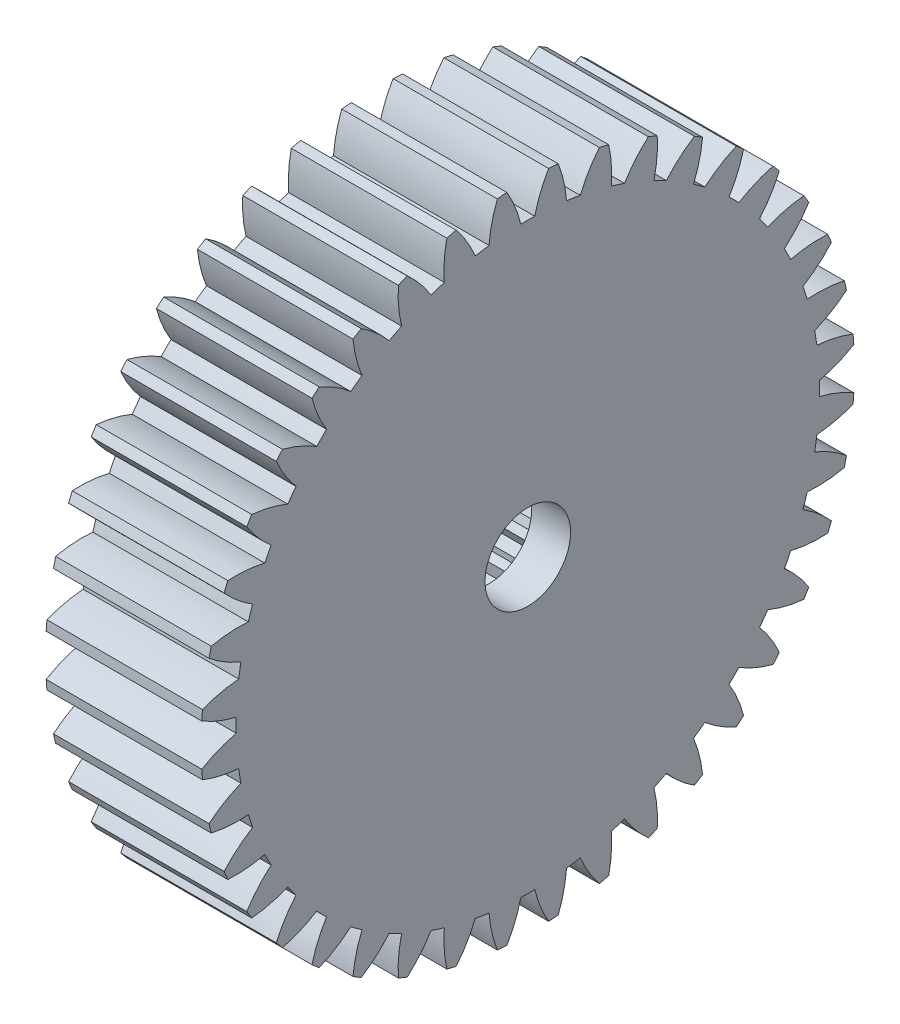
SolidWorks part; units mm, degrees
ref_plane "Front Plane" through (0, 0, 0) normal (0, 0, 1) x (1, 0, 0)
ref_plane "Top Plane" through (0, 0, 0) normal (0, 1, 0) x (1, 0, 0)
ref_plane "Right Plane" through (0, 0, 0) normal (1, 0, 0) x (0, 0, -1)
ref_plane "Plane1" through (-1.595, 0, 0) normal (1, 0, 0) x (0, 0, -1)
sketch "Sketch1" plane through (-1.595, 0, 0) normal (1, 0, 0) x (0, 0, -1)
  circle B0 centre (0, 0) radius 0.4
  arc B1 (-8.3829, 0.5357) -> (-7.4969, 0.179) centre (-6.7581, 3.2926) ccw
  arc B2 (-7.4969, 0.179) -> (-7.4969, -0.179) centre (0, 0) ccw
  arc B3 (-7.4969, -0.179) -> (-8.3829, -0.5357) centre (-6.7581, -3.2926) ccw
  arc B4 (-8.3829, -0.5357) -> (-8.3635, -0.7822) centre (0, 0) ccw
  arc B5 (-8.3635, -0.7822) -> (-7.4326, -0.996) centre (-7.19, 2.1948) ccw
  arc B6 (-7.4326, -0.996) -> (-7.3766, -1.3496) centre (0, 0) ccw
  arc B7 (-7.3766, -1.3496) -> (-8.1959, -1.8405) centre (-6.1599, -4.3092) ccw
  arc B8 (-8.1959, -1.8405) -> (-8.1382, -2.081) centre (0, 0) ccw
  arc B9 (-8.1382, -2.081) -> (-7.1853, -2.1464) centre (-7.4448, 1.043) ccw
  arc B10 (-7.1853, -2.1464) -> (-7.0746, -2.4869) centre (0, 0) ccw
  arc B11 (-7.0746, -2.4869) -> (-7.8071, -3.1) centre (-5.4099, -5.2198) ccw
  arc B12 (-7.8071, -3.1) -> (-7.7124, -3.3284) centre (0, 0) ccw
  arc B13 (-7.7124, -3.3284) -> (-6.761, -3.244) centre (-7.5163, -0.1344) ccw
  arc B14 (-6.761, -3.244) -> (-6.5985, -3.563) centre (0, 0) ccw
  arc B15 (-6.5985, -3.563) -> (-7.226, -4.2831) centre (-4.5268, -6.0018) ccw
  arc B16 (-7.226, -4.2831) -> (-7.0968, -4.4939) centre (0, 0) ccw
  arc B17 (-7.0968, -4.4939) -> (-6.1703, -4.2617) centre (-7.4028, -1.3086) ccw
  arc B18 (-6.1703, -4.2617) -> (-5.9599, -4.5514) centre (0, 0) ccw
  arc B19 (-5.9599, -4.5514) -> (-6.467, -5.3608) centre (-3.5321, -6.6361) ccw
  arc B20 (-6.467, -5.3608) -> (-6.3064, -5.5488) centre (0, 0) ccw
  arc B21 (-6.3064, -5.5488) -> (-5.4277, -5.1745) centre (-7.1069, -2.4505) ccw
  arc B22 (-5.4277, -5.1745) -> (-5.1745, -5.4277) centre (0, 0) ccw
  arc B23 (-5.1745, -5.4277) -> (-5.5488, -6.3064) centre (-2.4505, -7.1069) ccw
  arc B24 (-5.5488, -6.3064) -> (-5.3608, -6.467) centre (0, 0) ccw
  arc B25 (-5.3608, -6.467) -> (-4.5514, -5.9599) centre (-6.6361, -3.5321) ccw
  arc B26 (-4.5514, -5.9599) -> (-4.2617, -6.1703) centre (0, 0) ccw
  arc B27 (-4.2617, -6.1703) -> (-4.4939, -7.0968) centre (-1.3086, -7.4028) ccw
  arc B28 (-4.4939, -7.0968) -> (-4.2831, -7.226) centre (0, 0) ccw
  arc B29 (-4.2831, -7.226) -> (-3.563, -6.5985) centre (-6.0018, -4.5268) ccw
  arc B30 (-3.563, -6.5985) -> (-3.244, -6.761) centre (0, 0) ccw
  arc B31 (-3.244, -6.761) -> (-3.3284, -7.7124) centre (-0.1344, -7.5163) ccw
  arc B32 (-3.3284, -7.7124) -> (-3.1, -7.8071) centre (0, 0) ccw
  arc B33 (-3.1, -7.8071) -> (-2.4869, -7.0746) centre (-5.2198, -5.4099) ccw
  arc B34 (-2.4869, -7.0746) -> (-2.1464, -7.1853) centre (0, 0) ccw
  arc B35 (-2.1464, -7.1853) -> (-2.081, -8.1382) centre (1.043, -7.4448) ccw
  arc B36 (-2.081, -8.1382) -> (-1.8405, -8.1959) centre (0, 0) ccw
  arc B37 (-1.8405, -8.1959) -> (-1.3496, -7.3766) centre (-4.3092, -6.1599) ccw
  arc B38 (-1.3496, -7.3766) -> (-0.996, -7.4326) centre (0, 0) ccw
  arc B39 (-0.996, -7.4326) -> (-0.7822, -8.3635) centre (2.1948, -7.19) ccw
  arc B40 (-0.7822, -8.3635) -> (-0.5357, -8.3829) centre (0, 0) ccw
  arc B41 (-0.5357, -8.3829) -> (-0.179, -7.4969) centre (-3.2926, -6.7581) ccw
  arc B42 (-0.179, -7.4969) -> (0.179, -7.4969) centre (0, 0) ccw
  arc B43 (0.179, -7.4969) -> (0.5357, -8.3829) centre (3.2926, -6.7581) ccw
  arc B44 (0.5357, -8.3829) -> (0.7822, -8.3635) centre (0, 0) ccw
  arc B45 (0.7822, -8.3635) -> (0.996, -7.4326) centre (-2.1948, -7.19) ccw
  arc B46 (0.996, -7.4326) -> (1.3496, -7.3766) centre (0, 0) ccw
  arc B47 (1.3496, -7.3766) -> (1.8405, -8.1959) centre (4.3092, -6.1599) ccw
  arc B48 (1.8405, -8.1959) -> (2.081, -8.1382) centre (0, 0) ccw
  arc B49 (2.081, -8.1382) -> (2.1464, -7.1853) centre (-1.043, -7.4448) ccw
  arc B50 (2.1464, -7.1853) -> (2.4869, -7.0746) centre (0, 0) ccw
  arc B51 (2.4869, -7.0746) -> (3.1, -7.8071) centre (5.2198, -5.4099) ccw
  arc B52 (3.1, -7.8071) -> (3.3284, -7.7124) centre (0, 0) ccw
  arc B53 (3.3284, -7.7124) -> (3.244, -6.761) centre (0.1344, -7.5163) ccw
  arc B54 (3.244, -6.761) -> (3.563, -6.5985) centre (0, 0) ccw
  arc B55 (3.563, -6.5985) -> (4.2831, -7.226) centre (6.0018, -4.5268) ccw
  arc B56 (4.2831, -7.226) -> (4.4939, -7.0968) centre (0, 0) ccw
  arc B57 (4.4939, -7.0968) -> (4.2617, -6.1703) centre (1.3086, -7.4028) ccw
  arc B58 (4.2617, -6.1703) -> (4.5514, -5.9599) centre (0, 0) ccw
  arc B59 (4.5514, -5.9599) -> (5.3608, -6.467) centre (6.6361, -3.5321) ccw
  arc B60 (5.3608, -6.467) -> (5.5488, -6.3064) centre (0, 0) ccw
  arc B61 (5.5488, -6.3064) -> (5.1745, -5.4277) centre (2.4505, -7.1069) ccw
  arc B62 (5.1745, -5.4277) -> (5.4277, -5.1745) centre (0, 0) ccw
  arc B63 (5.4277, -5.1745) -> (6.3064, -5.5488) centre (7.1069, -2.4505) ccw
  arc B64 (6.3064, -5.5488) -> (6.467, -5.3608) centre (0, 0) ccw
  arc B65 (6.467, -5.3608) -> (5.9599, -4.5514) centre (3.5321, -6.6361) ccw
  arc B66 (5.9599, -4.5514) -> (6.1703, -4.2617) centre (0, 0) ccw
  arc B67 (6.1703, -4.2617) -> (7.0968, -4.4939) centre (7.4028, -1.3086) ccw
  arc B68 (7.0968, -4.4939) -> (7.226, -4.2831) centre (0, 0) ccw
  arc B69 (7.226, -4.2831) -> (6.5985, -3.563) centre (4.5268, -6.0018) ccw
  arc B70 (6.5985, -3.563) -> (6.761, -3.244) centre (0, 0) ccw
  arc B71 (6.761, -3.244) -> (7.7124, -3.3284) centre (7.5163, -0.1344) ccw
  arc B72 (7.7124, -3.3284) -> (7.8071, -3.1) centre (0, 0) ccw
  arc B73 (7.8071, -3.1) -> (7.0746, -2.4869) centre (5.4099, -5.2198) ccw
  arc B74 (7.0746, -2.4869) -> (7.1853, -2.1464) centre (0, 0) ccw
  arc B75 (7.1853, -2.1464) -> (8.1382, -2.081) centre (7.4448, 1.043) ccw
  arc B76 (8.1382, -2.081) -> (8.1959, -1.8405) centre (0, 0) ccw
  arc B77 (8.1959, -1.8405) -> (7.3766, -1.3496) centre (6.1599, -4.3092) ccw
  arc B78 (7.3766, -1.3496) -> (7.4326, -0.996) centre (0, 0) ccw
  arc B79 (7.4326, -0.996) -> (8.3635, -0.7822) centre (7.19, 2.1948) ccw
  arc B80 (8.3635, -0.7822) -> (8.3829, -0.5357) centre (0, 0) ccw
  arc B81 (8.3829, -0.5357) -> (7.4969, -0.179) centre (6.7581, -3.2926) ccw
  arc B82 (7.4969, -0.179) -> (7.4969, 0.179) centre (0, 0) ccw
  arc B83 (7.4969, 0.179) -> (8.3829, 0.5357) centre (6.7581, 3.2926) ccw
  arc B84 (8.3829, 0.5357) -> (8.3635, 0.7822) centre (0, 0) ccw
  arc B85 (8.3635, 0.7822) -> (7.4326, 0.996) centre (7.19, -2.1948) ccw
  arc B86 (7.4326, 0.996) -> (7.3766, 1.3496) centre (0, 0) ccw
  arc B87 (7.3766, 1.3496) -> (8.1959, 1.8405) centre (6.1599, 4.3092) ccw
  arc B88 (8.1959, 1.8405) -> (8.1382, 2.081) centre (0, 0) ccw
  arc B89 (8.1382, 2.081) -> (7.1853, 2.1464) centre (7.4448, -1.043) ccw
  arc B90 (7.1853, 2.1464) -> (7.0746, 2.4869) centre (0, 0) ccw
  arc B91 (7.0746, 2.4869) -> (7.8071, 3.1) centre (5.4099, 5.2198) ccw
  arc B92 (7.8071, 3.1) -> (7.7124, 3.3284) centre (0, 0) ccw
  arc B93 (7.7124, 3.3284) -> (6.761, 3.244) centre (7.5163, 0.1344) ccw
  arc B94 (6.761, 3.244) -> (6.5985, 3.563) centre (0, 0) ccw
  arc B95 (6.5985, 3.563) -> (7.226, 4.2831) centre (4.5268, 6.0018) ccw
  arc B96 (7.226, 4.2831) -> (7.0968, 4.4939) centre (0, 0) ccw
  arc B97 (7.0968, 4.4939) -> (6.1703, 4.2617) centre (7.4028, 1.3086) ccw
  arc B98 (6.1703, 4.2617) -> (5.9599, 4.5514) centre (0, 0) ccw
  arc B99 (5.9599, 4.5514) -> (6.467, 5.3608) centre (3.5321, 6.6361) ccw
  arc B100 (6.467, 5.3608) -> (6.3064, 5.5488) centre (0, 0) ccw
  arc B101 (6.3064, 5.5488) -> (5.4277, 5.1745) centre (7.1069, 2.4505) ccw
  arc B102 (5.4277, 5.1745) -> (5.1745, 5.4277) centre (0, 0) ccw
  arc B103 (5.1745, 5.4277) -> (5.5488, 6.3064) centre (2.4505, 7.1069) ccw
  arc B104 (5.5488, 6.3064) -> (5.3608, 6.467) centre (0, 0) ccw
  arc B105 (5.3608, 6.467) -> (4.5514, 5.9599) centre (6.6361, 3.5321) ccw
  arc B106 (4.5514, 5.9599) -> (4.2617, 6.1703) centre (0, 0) ccw
  arc B107 (4.2617, 6.1703) -> (4.4939, 7.0968) centre (1.3086, 7.4028) ccw
  arc B108 (4.4939, 7.0968) -> (4.2831, 7.226) centre (0, 0) ccw
  arc B109 (4.2831, 7.226) -> (3.563, 6.5985) centre (6.0018, 4.5268) ccw
  arc B110 (3.563, 6.5985) -> (3.244, 6.761) centre (0, 0) ccw
  arc B111 (3.244, 6.761) -> (3.3284, 7.7124) centre (0.1344, 7.5163) ccw
  arc B112 (3.3284, 7.7124) -> (3.1, 7.8071) centre (0, 0) ccw
  arc B113 (3.1, 7.8071) -> (2.4869, 7.0746) centre (5.2198, 5.4099) ccw
  arc B114 (2.4869, 7.0746) -> (2.1464, 7.1853) centre (0, 0) ccw
  arc B115 (2.1464, 7.1853) -> (2.081, 8.1382) centre (-1.043, 7.4448) ccw
  arc B116 (2.081, 8.1382) -> (1.8405, 8.1959) centre (0, 0) ccw
  arc B117 (1.8405, 8.1959) -> (1.3496, 7.3766) centre (4.3092, 6.1599) ccw
  arc B118 (1.3496, 7.3766) -> (0.996, 7.4326) centre (0, 0) ccw
  arc B119 (0.996, 7.4326) -> (0.7822, 8.3635) centre (-2.1948, 7.19) ccw
  arc B120 (0.7822, 8.3635) -> (0.5357, 8.3829) centre (0, 0) ccw
  arc B121 (0.5357, 8.3829) -> (0.179, 7.4969) centre (3.2926, 6.7581) ccw
  arc B122 (0.179, 7.4969) -> (-0.179, 7.4969) centre (0, 0) ccw
  arc B123 (-0.179, 7.4969) -> (-0.5357, 8.3829) centre (-3.2926, 6.7581) ccw
  arc B124 (-0.5357, 8.3829) -> (-0.7822, 8.3635) centre (0, 0) ccw
  arc B125 (-0.7822, 8.3635) -> (-0.996, 7.4326) centre (2.1948, 7.19) ccw
  arc B126 (-0.996, 7.4326) -> (-1.3496, 7.3766) centre (0, 0) ccw
  arc B127 (-1.3496, 7.3766) -> (-1.8405, 8.1959) centre (-4.3092, 6.1599) ccw
  arc B128 (-1.8405, 8.1959) -> (-2.081, 8.1382) centre (0, 0) ccw
  arc B129 (-2.081, 8.1382) -> (-2.1464, 7.1853) centre (1.043, 7.4448) ccw
  arc B130 (-2.1464, 7.1853) -> (-2.4869, 7.0746) centre (0, 0) ccw
  arc B131 (-2.4869, 7.0746) -> (-3.1, 7.8071) centre (-5.2198, 5.4099) ccw
  arc B132 (-3.1, 7.8071) -> (-3.3284, 7.7124) centre (0, 0) ccw
  arc B133 (-3.3284, 7.7124) -> (-3.244, 6.761) centre (-0.1344, 7.5163) ccw
  arc B134 (-3.244, 6.761) -> (-3.563, 6.5985) centre (0, 0) ccw
  arc B135 (-3.563, 6.5985) -> (-4.2831, 7.226) centre (-6.0018, 4.5268) ccw
  arc B136 (-4.2831, 7.226) -> (-4.4939, 7.0968) centre (0, 0) ccw
  arc B137 (-4.4939, 7.0968) -> (-4.2617, 6.1703) centre (-1.3086, 7.4028) ccw
  arc B138 (-4.2617, 6.1703) -> (-4.5514, 5.9599) centre (0, 0) ccw
  arc B139 (-4.5514, 5.9599) -> (-5.3608, 6.467) centre (-6.6361, 3.5321) ccw
  arc B140 (-5.3608, 6.467) -> (-5.5488, 6.3064) centre (0, 0) ccw
  arc B141 (-5.5488, 6.3064) -> (-5.1745, 5.4277) centre (-2.4505, 7.1069) ccw
  arc B142 (-5.1745, 5.4277) -> (-5.4277, 5.1745) centre (0, 0) ccw
  arc B143 (-5.4277, 5.1745) -> (-6.3064, 5.5488) centre (-7.1069, 2.4505) ccw
  arc B144 (-6.3064, 5.5488) -> (-6.467, 5.3608) centre (0, 0) ccw
  arc B145 (-6.467, 5.3608) -> (-5.9599, 4.5514) centre (-3.5321, 6.6361) ccw
  arc B146 (-5.9599, 4.5514) -> (-6.1703, 4.2617) centre (0, 0) ccw
  arc B147 (-6.1703, 4.2617) -> (-7.0968, 4.4939) centre (-7.4028, 1.3086) ccw
  arc B148 (-7.0968, 4.4939) -> (-7.226, 4.2831) centre (0, 0) ccw
  arc B149 (-7.226, 4.2831) -> (-6.5985, 3.563) centre (-4.5268, 6.0018) ccw
  arc B150 (-6.5985, 3.563) -> (-6.761, 3.244) centre (0, 0) ccw
  arc B151 (-6.761, 3.244) -> (-7.7124, 3.3284) centre (-7.5163, 0.1344) ccw
  arc B152 (-7.7124, 3.3284) -> (-7.8071, 3.1) centre (0, 0) ccw
  arc B153 (-7.8071, 3.1) -> (-7.0746, 2.4869) centre (-5.4099, 5.2198) ccw
  arc B154 (-7.0746, 2.4869) -> (-7.1853, 2.1464) centre (0, 0) ccw
  arc B155 (-7.1853, 2.1464) -> (-8.1382, 2.081) centre (-7.4448, -1.043) ccw
  arc B156 (-8.1382, 2.081) -> (-8.1959, 1.8405) centre (0, 0) ccw
  arc B157 (-8.1959, 1.8405) -> (-7.3766, 1.3496) centre (-6.1599, 4.3092) ccw
  arc B158 (-7.3766, 1.3496) -> (-7.4326, 0.996) centre (0, 0) ccw
  arc B159 (-7.4326, 0.996) -> (-8.3635, 0.7822) centre (-7.19, -2.1948) ccw
  arc B160 (-8.3635, 0.7822) -> (-8.3829, 0.5357) centre (0, 0) ccw
sketch_block_instance "Block2-1"
sketch_block "Block2"
extrude "Boss-Extrude1" add sketch "Sketch1" against normal blind 3
sketch "Sketch2" plane through (-1.595, 0, 0) normal (1, 0, 0) x (0, 0, -1)
  arc B0 (-1.95, 0) -> (-1.8546, -0.6026) centre (0, 0) ccw
  arc B1 (-1.8546, -0.6026) -> (-1.5776, -1.1462) centre (0, 0) ccw
  arc B2 (-1.5776, -1.1462) -> (-1.1462, -1.5776) centre (0, 0) ccw
  arc B3 (-1.1462, -1.5776) -> (-0.6026, -1.8546) centre (0, 0) ccw
  arc B4 (-0.6026, -1.8546) -> (0, -1.95) centre (0, 0) ccw
  arc B5 (0, -1.95) -> (0.6026, -1.8546) centre (0, 0) ccw
  arc B6 (0.6026, -1.8546) -> (1.1462, -1.5776) centre (0, 0) ccw
  arc B7 (1.1462, -1.5776) -> (1.5776, -1.1462) centre (0, 0) ccw
  arc B8 (1.5776, -1.1462) -> (1.8546, -0.6026) centre (0, 0) ccw
  arc B9 (1.8546, -0.6026) -> (1.95, 0) centre (0, 0) ccw
  arc B10 (1.95, 0) -> (1.8546, 0.6026) centre (0, 0) ccw
  arc B11 (1.8546, 0.6026) -> (1.5776, 1.1462) centre (0, 0) ccw
  arc B12 (1.5776, 1.1462) -> (1.1462, 1.5776) centre (0, 0) ccw
  arc B13 (1.1462, 1.5776) -> (0.6026, 1.8546) centre (0, 0) ccw
  arc B14 (0.6026, 1.8546) -> (0, 1.95) centre (0, 0) ccw
  arc B15 (0, 1.95) -> (-0.6026, 1.8546) centre (0, 0) ccw
  arc B16 (-0.6026, 1.8546) -> (-1.1462, 1.5776) centre (0, 0) ccw
  arc B17 (-1.1462, 1.5776) -> (-1.5776, 1.1462) centre (0, 0) ccw
  arc B18 (-1.5776, 1.1462) -> (-1.8546, 0.6026) centre (0, 0) ccw
  arc B19 (-1.8546, 0.6026) -> (-1.95, 0) centre (0, 0) ccw
  arc B20 (-1.6348, 1.8248) -> (-1.8248, 1.6348) centre (0, 0) ccw
  arc B21 (-1.1462, 1.5776) -> (-1.5776, 1.1462) centre (0, 0) ccw
  arc B22 (-2.1187, 1.2303) -> (-2.2407, 0.9909) centre (0, 0) ccw
  arc B23 (-1.5776, 1.1462) -> (-1.8546, 0.6026) centre (0, 0) ccw
  arc B24 (-2.3952, 0.5154) -> (-2.4372, 0.25) centre (0, 0) ccw
  arc B25 (-1.8546, 0.6026) -> (-1.95, 0) centre (0, 0) ccw
  arc B26 (-1.95, 0) -> (-1.8546, -0.6026) centre (0, 0) ccw
  arc B27 (-2.4372, -0.25) -> (-2.3952, -0.5154) centre (0, 0) ccw
  arc B28 (-1.8546, -0.6026) -> (-1.5776, -1.1462) centre (0, 0) ccw
  arc B29 (-2.2407, -0.9909) -> (-2.1187, -1.2303) centre (0, 0) ccw
  arc B30 (-1.5776, -1.1462) -> (-1.1462, -1.5776) centre (0, 0) ccw
  arc B31 (-1.8248, -1.6348) -> (-1.6348, -1.8248) centre (0, 0) ccw
  arc B32 (-1.1462, -1.5776) -> (-0.6026, -1.8546) centre (0, 0) ccw
  arc B33 (-1.2303, -2.1187) -> (-0.9909, -2.2407) centre (0, 0) ccw
  arc B34 (-0.6026, -1.8546) -> (0, -1.95) centre (0, 0) ccw
  arc B35 (-0.5154, -2.3952) -> (-0.25, -2.4372) centre (0, 0) ccw
  arc B36 (0, -1.95) -> (0.6026, -1.8546) centre (0, 0) ccw
  arc B37 (0.25, -2.4372) -> (0.5154, -2.3952) centre (0, 0) ccw
  arc B38 (0.6026, -1.8546) -> (1.1462, -1.5776) centre (0, 0) ccw
  arc B39 (0.9909, -2.2407) -> (1.2303, -2.1187) centre (0, 0) ccw
  arc B40 (1.6348, -1.8248) -> (1.8248, -1.6348) centre (0, 0) ccw
  arc B41 (1.1462, -1.5776) -> (1.5776, -1.1462) centre (0, 0) ccw
  arc B42 (1.5776, -1.1462) -> (1.8546, -0.6026) centre (0, 0) ccw
  arc B43 (2.1187, -1.2303) -> (2.2407, -0.9909) centre (0, 0) ccw
  arc B44 (1.8546, -0.6026) -> (1.95, 0) centre (0, 0) ccw
  arc B45 (2.3952, -0.5154) -> (2.4372, -0.25) centre (0, 0) ccw
  arc B46 (1.95, 0) -> (1.8546, 0.6026) centre (0, 0) ccw
  arc B47 (2.4372, 0.25) -> (2.3952, 0.5154) centre (0, 0) ccw
  arc B48 (2.2407, 0.9909) -> (2.1187, 1.2303) centre (0, 0) ccw
  arc B49 (1.8546, 0.6026) -> (1.5776, 1.1462) centre (0, 0) ccw
  arc B50 (1.8248, 1.6348) -> (1.6348, 1.8248) centre (0, 0) ccw
  arc B51 (1.5776, 1.1462) -> (1.1462, 1.5776) centre (0, 0) ccw
  arc B52 (1.2303, 2.1187) -> (0.9909, 2.2407) centre (0, 0) ccw
  arc B53 (1.1462, 1.5776) -> (0.6026, 1.8546) centre (0, 0) ccw
  arc B54 (0.6026, 1.8546) -> (0, 1.95) centre (0, 0) ccw
  arc B55 (0.5154, 2.3952) -> (0.25, 2.4372) centre (0, 0) ccw
  arc B56 (0, 1.95) -> (-0.6026, 1.8546) centre (0, 0) ccw
  arc B57 (-0.25, 2.4372) -> (-0.5154, 2.3952) centre (0, 0) ccw
  arc B58 (-0.6026, 1.8546) -> (-1.1462, 1.5776) centre (0, 0) ccw
  arc B59 (-0.9909, 2.2407) -> (-1.2303, 2.1187) centre (0, 0) ccw
  spline B60 degree 3 poles (-1.1462, 1.5776) (-1.2233, 1.6166) (-1.3868, 1.6994) (-1.5491, 1.7815) (-1.6348, 1.8248) knots 0 0 0 0 0.472059 1 1 1 1
  spline B61 degree 3 poles (-1.8248, 1.6348) (-1.7815, 1.5491) (-1.6994, 1.3868) (-1.6166, 1.2233) (-1.5776, 1.1462) knots 0 0 0 0 0.527941 1 1 1 1
  spline B62 degree 3 poles (-1.5776, 1.1462) (-1.663, 1.1595) (-1.8441, 1.1877) (-2.0238, 1.2156) (-2.1187, 1.2303) knots 0 0 0 0 0.472059 1 1 1 1
  spline B63 degree 3 poles (-2.2407, 0.9909) (-2.173, 0.9228) (-2.0448, 0.7938) (-1.9156, 0.6639) (-1.8546, 0.6026) knots 0 0 0 0 0.527941 1 1 1 1
  spline B64 degree 3 poles (-1.8546, 0.6026) (-1.94, 0.5888) (-2.1208, 0.5597) (-2.3004, 0.5307) (-2.3952, 0.5154) knots 0 0 0 0 0.472059 1 1 1 1
  spline B65 degree 3 poles (-2.4372, 0.25) (-2.3518, 0.2061) (-2.19, 0.1231) (-2.027, 0.0395) (-1.95, 0) knots 0 0 0 0 0.527941 1 1 1 1
  spline B66 degree 3 poles (-2.3952, -0.5154) (-2.3004, -0.5307) (-2.1208, -0.5597) (-1.94, -0.5888) (-1.8546, -0.6026) knots 0 0 0 0 0.527941 1 1 1 1
  spline B67 degree 3 poles (-1.95, 0) (-2.027, -0.0395) (-2.19, -0.1231) (-2.3518, -0.2061) (-2.4372, -0.25) knots 0 0 0 0 0.472059 1 1 1 1
  spline B68 degree 3 poles (-2.1187, -1.2303) (-2.0238, -1.2156) (-1.8441, -1.1877) (-1.663, -1.1595) (-1.5776, -1.1462) knots 0 0 0 0 0.527941 1 1 1 1
  spline B69 degree 3 poles (-1.8546, -0.6026) (-1.9156, -0.6639) (-2.0448, -0.7938) (-2.173, -0.9228) (-2.2407, -0.9909) knots 0 0 0 0 0.472059 1 1 1 1
  spline B70 degree 3 poles (-1.6348, -1.8248) (-1.5491, -1.7815) (-1.3868, -1.6994) (-1.2233, -1.6166) (-1.1462, -1.5776) knots 0 0 0 0 0.527941 1 1 1 1
  spline B71 degree 3 poles (-1.5776, -1.1462) (-1.6166, -1.2233) (-1.6994, -1.3868) (-1.7815, -1.5491) (-1.8248, -1.6348) knots 0 0 0 0 0.472059 1 1 1 1
  spline B72 degree 3 poles (-0.9909, -2.2407) (-0.9228, -2.173) (-0.7938, -2.0448) (-0.6639, -1.9156) (-0.6026, -1.8546) knots 0 0 0 0 0.527941 1 1 1 1
  spline B73 degree 3 poles (-1.1462, -1.5776) (-1.1595, -1.663) (-1.1877, -1.8441) (-1.2156, -2.0238) (-1.2303, -2.1187) knots 0 0 0 0 0.472059 1 1 1 1
  spline B74 degree 3 poles (-0.25, -2.4372) (-0.2061, -2.3518) (-0.1231, -2.19) (-0.0395, -2.027) (0, -1.95) knots 0 0 0 0 0.527941 1 1 1 1
  spline B75 degree 3 poles (-0.6026, -1.8546) (-0.5888, -1.94) (-0.5597, -2.1208) (-0.5307, -2.3004) (-0.5154, -2.3952) knots 0 0 0 0 0.472059 1 1 1 1
  spline B76 degree 3 poles (0.5154, -2.3952) (0.5307, -2.3004) (0.5597, -2.1208) (0.5888, -1.94) (0.6026, -1.8546) knots 0 0 0 0 0.527941 1 1 1 1
  spline B77 degree 3 poles (0, -1.95) (0.0395, -2.027) (0.1231, -2.19) (0.2061, -2.3518) (0.25, -2.4372) knots 0 0 0 0 0.472059 1 1 1 1
  spline B78 degree 3 poles (1.2303, -2.1187) (1.2156, -2.0238) (1.1877, -1.8441) (1.1595, -1.663) (1.1462, -1.5776) knots 0 0 0 0 0.527941 1 1 1 1
  spline B79 degree 3 poles (0.6026, -1.8546) (0.6639, -1.9156) (0.7938, -2.0448) (0.9228, -2.173) (0.9909, -2.2407) knots 0 0 0 0 0.472059 1 1 1 1
  spline B80 degree 3 poles (1.1462, -1.5776) (1.2233, -1.6166) (1.3868, -1.6994) (1.5491, -1.7815) (1.6348, -1.8248) knots 0 0 0 0 0.472059 1 1 1 1
  spline B81 degree 3 poles (1.8248, -1.6348) (1.7815, -1.5491) (1.6994, -1.3868) (1.6166, -1.2233) (1.5776, -1.1462) knots 0 0 0 0 0.527941 1 1 1 1
  spline B82 degree 3 poles (2.2407, -0.9909) (2.173, -0.9228) (2.0448, -0.7938) (1.9156, -0.6639) (1.8546, -0.6026) knots 0 0 0 0 0.527941 1 1 1 1
  spline B83 degree 3 poles (1.5776, -1.1462) (1.663, -1.1595) (1.8441, -1.1877) (2.0238, -1.2156) (2.1187, -1.2303) knots 0 0 0 0 0.472059 1 1 1 1
  spline B84 degree 3 poles (2.4372, -0.25) (2.3518, -0.2061) (2.19, -0.1231) (2.027, -0.0395) (1.95, 0) knots 0 0 0 0 0.527941 1 1 1 1
  spline B85 degree 3 poles (1.8546, -0.6026) (1.94, -0.5888) (2.1208, -0.5597) (2.3004, -0.5307) (2.3952, -0.5154) knots 0 0 0 0 0.472059 1 1 1 1
  spline B86 degree 3 poles (2.3952, 0.5154) (2.3004, 0.5307) (2.1208, 0.5597) (1.94, 0.5888) (1.8546, 0.6026) knots 0 0 0 0 0.527941 1 1 1 1
  spline B87 degree 3 poles (1.95, 0) (2.027, 0.0395) (2.19, 0.1231) (2.3518, 0.2061) (2.4372, 0.25) knots 0 0 0 0 0.472059 1 1 1 1
  spline B88 degree 3 poles (1.8546, 0.6026) (1.9156, 0.6639) (2.0448, 0.7938) (2.173, 0.9228) (2.2407, 0.9909) knots 0 0 0 0 0.472059 1 1 1 1
  spline B89 degree 3 poles (2.1187, 1.2303) (2.0238, 1.2156) (1.8441, 1.1877) (1.663, 1.1595) (1.5776, 1.1462) knots 0 0 0 0 0.527941 1 1 1 1
  spline B90 degree 3 poles (1.5776, 1.1462) (1.6166, 1.2233) (1.6994, 1.3868) (1.7815, 1.5491) (1.8248, 1.6348) knots 0 0 0 0 0.472059 1 1 1 1
  spline B91 degree 3 poles (1.6348, 1.8248) (1.5491, 1.7815) (1.3868, 1.6994) (1.2233, 1.6166) (1.1462, 1.5776) knots 0 0 0 0 0.527941 1 1 1 1
  spline B92 degree 3 poles (1.1462, 1.5776) (1.1595, 1.663) (1.1877, 1.8441) (1.2156, 2.0238) (1.2303, 2.1187) knots 0 0 0 0 0.472059 1 1 1 1
  spline B93 degree 3 poles (0.9909, 2.2407) (0.9228, 2.173) (0.7938, 2.0448) (0.6639, 1.9156) (0.6026, 1.8546) knots 0 0 0 0 0.527941 1 1 1 1
  spline B94 degree 3 poles (0.25, 2.4372) (0.2061, 2.3518) (0.1231, 2.19) (0.0395, 2.027) (0, 1.95) knots 0 0 0 0 0.527941 1 1 1 1
  spline B95 degree 3 poles (0.6026, 1.8546) (0.5888, 1.94) (0.5597, 2.1208) (0.5307, 2.3004) (0.5154, 2.3952) knots 0 0 0 0 0.472059 1 1 1 1
  spline B96 degree 3 poles (-0.5154, 2.3952) (-0.5307, 2.3004) (-0.5597, 2.1208) (-0.5888, 1.94) (-0.6026, 1.8546) knots 0 0 0 0 0.527941 1 1 1 1
  spline B97 degree 3 poles (0, 1.95) (-0.0395, 2.027) (-0.1231, 2.19) (-0.2061, 2.3518) (-0.25, 2.4372) knots 0 0 0 0 0.472059 1 1 1 1
  spline B98 degree 3 poles (-1.2303, 2.1187) (-1.2156, 2.0238) (-1.1877, 1.8441) (-1.1595, 1.663) (-1.1462, 1.5776) knots 0 0 0 0 0.527941 1 1 1 1
  spline B99 degree 3 poles (-0.6026, 1.8546) (-0.6639, 1.9156) (-0.7938, 2.0448) (-0.9228, 2.173) (-0.9909, 2.2407) knots 0 0 0 0 0.472059 1 1 1 1
sketch_block_instance "Block1-1"
sketch_block "Block1"
extrude "Cut-Extrude1" cut sketch "Sketch2" against normal through all contours B18 B19 B0 B1 B2 B3 B4 B5 B6 B7 B8 B9 B10 B11 B12 B13 B14 B15 B16 B17 | B0 B67 B27 B66 | B24 B65 B19 B64 | B20 B61 B17 B60 | B22 B63 B18 B62 | B16 B99 B59 B98 | B15 B97 B57 B96 | B14 B95 B55 B94 | B52 B93 B13 B92 | B50 B91 B12 B90 | B48 B89 B11 B88 | B10 B87 B47 B86 | B9 B85 B45 B84 | B8 B83 B43 B82 | B40 B81 B7 B80 | B6 B79 B39 B78 | B5 B77 B37 B76 | B4 B75 B35 B74 | B3 B73 B33 B72 | B2 B71 B31 B70 | B1 B69 B29 B68 region at (-1.595, 0, 0) region at (-1.595, 0.3384, 2.1364) region at (-1.595, -0.3384, 2.1364) region at (-1.595, -0.982, 1.9273) region at (-1.595, 0.982, 1.9273) region at (-1.595, -1.5295, 1.5295) region at (-1.595, 1.5295, 1.5295) region at (-1.595, -1.9273, 0.982) region at (-1.595, 1.9273, 0.982) region at (-1.595, -2.1364, 0.3384) region at (-1.595, 2.1364, 0.3384) region at (-1.595, -2.1364, -0.3384) region at (-1.595, 2.1364, -0.3384) region at (-1.595, -1.9273, -0.982) region at (-1.595, 1.9273, -0.982) region at (-1.595, -1.5295, -1.5295) region at (-1.595, 1.5295, -1.5295) region at (-1.595, -0.982, -1.9273) region at (-1.595, 0.982, -1.9273) region at (-1.595, -0.3384, -2.1364) region at (-1.595, 0.3384, -2.1364)
sketch "Sketch4" plane through (-1.595, 0, 0) normal (1, 0, 0) x (0, 0, -1)
  circle A0 centre (0, 0) radius 2.15
  dimension "D1" = 4.3
extrude "Cut-Extrude2" cut sketch "Sketch4" against normal through all
sketch "Sketch5" plane through (-1.595, 0, 0) normal (1, 0, 0) x (0, 0, -1)
  arc A160 (-8.3635, 0.7822) -> (-8.3829, 0.5357) centre (0, 0) ccw
  arc A161 (-8.3829, 0.5357) -> (-7.4969, 0.179) centre (-6.7581, 3.2926) ccw
  arc A162 (-7.4969, 0.179) -> (-7.4969, -0.179) centre (0, 0) ccw
  arc A163 (-7.4969, -0.179) -> (-8.3829, -0.5357) centre (-6.7581, -3.2926) ccw
  arc A164 (-8.3829, -0.5357) -> (-8.3635, -0.7822) centre (0, 0) ccw
  arc A165 (-8.3635, -0.7822) -> (-7.4326, -0.996) centre (-7.19, 2.1948) ccw
  arc A166 (-7.4326, -0.996) -> (-7.3766, -1.3496) centre (0, 0) ccw
  arc A167 (-7.3766, -1.3496) -> (-8.1959, -1.8405) centre (-6.1599, -4.3092) ccw
  arc A168 (-8.1959, -1.8405) -> (-8.1382, -2.081) centre (0, 0) ccw
  arc A169 (-8.1382, -2.081) -> (-7.1853, -2.1464) centre (-7.4448, 1.043) ccw
  arc A170 (-7.1853, -2.1464) -> (-7.0746, -2.4869) centre (0, 0) ccw
  arc A171 (-7.0746, -2.4869) -> (-7.8071, -3.1) centre (-5.4099, -5.2198) ccw
  arc A172 (-7.8071, -3.1) -> (-7.7124, -3.3284) centre (0, 0) ccw
  arc A173 (-7.7124, -3.3284) -> (-6.761, -3.244) centre (-7.5163, -0.1344) ccw
  arc A174 (-6.761, -3.244) -> (-6.5985, -3.563) centre (0, 0) ccw
  arc A175 (-6.5985, -3.563) -> (-7.226, -4.2831) centre (-4.5268, -6.0018) ccw
  arc A176 (-7.226, -4.2831) -> (-7.0968, -4.4939) centre (0, 0) ccw
  arc A177 (-7.0968, -4.4939) -> (-6.1703, -4.2617) centre (-7.4028, -1.3086) ccw
  arc A178 (-6.1703, -4.2617) -> (-5.9599, -4.5514) centre (0, 0) ccw
  arc A179 (-5.9599, -4.5514) -> (-6.467, -5.3608) centre (-3.5321, -6.6361) ccw
  arc A180 (-6.467, -5.3608) -> (-6.3064, -5.5488) centre (0, 0) ccw
  arc A181 (-6.3064, -5.5488) -> (-5.4277, -5.1745) centre (-7.1069, -2.4505) ccw
  arc A182 (-5.4277, -5.1745) -> (-5.1745, -5.4277) centre (0, 0) ccw
  arc A183 (-5.1745, -5.4277) -> (-5.5488, -6.3064) centre (-2.4505, -7.1069) ccw
  arc A184 (-5.5488, -6.3064) -> (-5.3608, -6.467) centre (0, 0) ccw
  arc A185 (-5.3608, -6.467) -> (-4.5514, -5.9599) centre (-6.6361, -3.5321) ccw
  arc A186 (-4.5514, -5.9599) -> (-4.2617, -6.1703) centre (0, 0) ccw
  arc A187 (-4.2617, -6.1703) -> (-4.4939, -7.0968) centre (-1.3086, -7.4028) ccw
  arc A188 (-4.4939, -7.0968) -> (-4.2831, -7.226) centre (0, 0) ccw
  arc A189 (-4.2831, -7.226) -> (-3.563, -6.5985) centre (-6.0018, -4.5268) ccw
  arc A190 (-3.563, -6.5985) -> (-3.244, -6.761) centre (0, 0) ccw
  arc A191 (-3.244, -6.761) -> (-3.3284, -7.7124) centre (-0.1344, -7.5163) ccw
  arc A192 (-3.3284, -7.7124) -> (-3.1, -7.8071) centre (0, 0) ccw
  arc A193 (-3.1, -7.8071) -> (-2.4869, -7.0746) centre (-5.2198, -5.4099) ccw
  arc A194 (-2.4869, -7.0746) -> (-2.1464, -7.1853) centre (0, 0) ccw
  arc A195 (-2.1464, -7.1853) -> (-2.081, -8.1382) centre (1.043, -7.4448) ccw
  arc A196 (-2.081, -8.1382) -> (-1.8405, -8.1959) centre (0, 0) ccw
  arc A197 (-1.8405, -8.1959) -> (-1.3496, -7.3766) centre (-4.3092, -6.1599) ccw
  arc A198 (-1.3496, -7.3766) -> (-0.996, -7.4326) centre (0, 0) ccw
  arc A199 (-0.996, -7.4326) -> (-0.7822, -8.3635) centre (2.1948, -7.19) ccw
  arc A200 (-0.7822, -8.3635) -> (-0.5357, -8.3829) centre (0, 0) ccw
  arc A201 (-0.5357, -8.3829) -> (-0.179, -7.4969) centre (-3.2926, -6.7581) ccw
  arc A202 (-0.179, -7.4969) -> (0.179, -7.4969) centre (0, 0) ccw
  arc A203 (0.179, -7.4969) -> (0.5357, -8.3829) centre (3.2926, -6.7581) ccw
  arc A204 (0.5357, -8.3829) -> (0.7822, -8.3635) centre (0, 0) ccw
  arc A205 (0.7822, -8.3635) -> (0.996, -7.4326) centre (-2.1948, -7.19) ccw
  arc A206 (0.996, -7.4326) -> (1.3496, -7.3766) centre (0, 0) ccw
  arc A207 (1.3496, -7.3766) -> (1.8405, -8.1959) centre (4.3092, -6.1599) ccw
  arc A208 (1.8405, -8.1959) -> (2.081, -8.1382) centre (0, 0) ccw
  arc A209 (2.081, -8.1382) -> (2.1464, -7.1853) centre (-1.043, -7.4448) ccw
  arc A210 (2.1464, -7.1853) -> (2.4869, -7.0746) centre (0, 0) ccw
  arc A211 (2.4869, -7.0746) -> (3.1, -7.8071) centre (5.2198, -5.4099) ccw
  arc A212 (3.1, -7.8071) -> (3.3284, -7.7124) centre (0, 0) ccw
  arc A213 (3.3284, -7.7124) -> (3.244, -6.761) centre (0.1344, -7.5163) ccw
  arc A214 (3.244, -6.761) -> (3.563, -6.5985) centre (0, 0) ccw
  arc A215 (3.563, -6.5985) -> (4.2831, -7.226) centre (6.0018, -4.5268) ccw
  arc A216 (4.2831, -7.226) -> (4.4939, -7.0968) centre (0, 0) ccw
  arc A217 (4.4939, -7.0968) -> (4.2617, -6.1703) centre (1.3086, -7.4028) ccw
  arc A218 (4.2617, -6.1703) -> (4.5514, -5.9599) centre (0, 0) ccw
  arc A219 (4.5514, -5.9599) -> (5.3608, -6.467) centre (6.6361, -3.5321) ccw
  arc A220 (5.3608, -6.467) -> (5.5488, -6.3064) centre (0, 0) ccw
  arc A221 (5.5488, -6.3064) -> (5.1745, -5.4277) centre (2.4505, -7.1069) ccw
  arc A222 (5.1745, -5.4277) -> (5.4277, -5.1745) centre (0, 0) ccw
  arc A223 (5.4277, -5.1745) -> (6.3064, -5.5488) centre (7.1069, -2.4505) ccw
  arc A224 (6.3064, -5.5488) -> (6.467, -5.3608) centre (0, 0) ccw
  arc A225 (6.467, -5.3608) -> (5.9599, -4.5514) centre (3.5321, -6.6361) ccw
  arc A226 (5.9599, -4.5514) -> (6.1703, -4.2617) centre (0, 0) ccw
  arc A227 (6.1703, -4.2617) -> (7.0968, -4.4939) centre (7.4028, -1.3086) ccw
  arc A228 (7.0968, -4.4939) -> (7.226, -4.2831) centre (0, 0) ccw
  arc A229 (7.226, -4.2831) -> (6.5985, -3.563) centre (4.5268, -6.0018) ccw
  arc A230 (6.5985, -3.563) -> (6.761, -3.244) centre (0, 0) ccw
  arc A231 (6.761, -3.244) -> (7.7124, -3.3284) centre (7.5163, -0.1344) ccw
  arc A232 (7.7124, -3.3284) -> (7.8071, -3.1) centre (0, 0) ccw
  arc A233 (7.8071, -3.1) -> (7.0746, -2.4869) centre (5.4099, -5.2198) ccw
  arc A234 (7.0746, -2.4869) -> (7.1853, -2.1464) centre (0, 0) ccw
  arc A235 (7.1853, -2.1464) -> (8.1382, -2.081) centre (7.4448, 1.043) ccw
  arc A236 (8.1382, -2.081) -> (8.1959, -1.8405) centre (0, 0) ccw
  arc A237 (8.1959, -1.8405) -> (7.3766, -1.3496) centre (6.1599, -4.3092) ccw
  arc A238 (7.3766, -1.3496) -> (7.4326, -0.996) centre (0, 0) ccw
  arc A239 (7.4326, -0.996) -> (8.3635, -0.7822) centre (7.19, 2.1948) ccw
  arc A240 (8.3635, -0.7822) -> (8.3829, -0.5357) centre (0, 0) ccw
  arc A241 (8.3829, -0.5357) -> (7.4969, -0.179) centre (6.7581, -3.2926) ccw
  arc A242 (7.4969, -0.179) -> (7.4969, 0.179) centre (0, 0) ccw
  arc A243 (7.4969, 0.179) -> (8.3829, 0.5357) centre (6.7581, 3.2926) ccw
  arc A244 (8.3829, 0.5357) -> (8.3635, 0.7822) centre (0, 0) ccw
  arc A245 (8.3635, 0.7822) -> (7.4326, 0.996) centre (7.19, -2.1948) ccw
  arc A246 (7.4326, 0.996) -> (7.3766, 1.3496) centre (0, 0) ccw
  arc A247 (7.3766, 1.3496) -> (8.1959, 1.8405) centre (6.1599, 4.3092) ccw
  arc A248 (8.1959, 1.8405) -> (8.1382, 2.081) centre (0, 0) ccw
  arc A249 (8.1382, 2.081) -> (7.1853, 2.1464) centre (7.4448, -1.043) ccw
  arc A250 (7.1853, 2.1464) -> (7.0746, 2.4869) centre (0, 0) ccw
  arc A251 (7.0746, 2.4869) -> (7.8071, 3.1) centre (5.4099, 5.2198) ccw
  arc A252 (7.8071, 3.1) -> (7.7124, 3.3284) centre (0, 0) ccw
  arc A253 (7.7124, 3.3284) -> (6.761, 3.244) centre (7.5163, 0.1344) ccw
  arc A254 (6.761, 3.244) -> (6.5985, 3.563) centre (0, 0) ccw
  arc A255 (6.5985, 3.563) -> (7.226, 4.2831) centre (4.5268, 6.0018) ccw
  arc A256 (7.226, 4.2831) -> (7.0968, 4.4939) centre (0, 0) ccw
  arc A257 (7.0968, 4.4939) -> (6.1703, 4.2617) centre (7.4028, 1.3086) ccw
  arc A258 (6.1703, 4.2617) -> (5.9599, 4.5514) centre (0, 0) ccw
  arc A259 (5.9599, 4.5514) -> (6.467, 5.3608) centre (3.5321, 6.6361) ccw
  arc A260 (6.467, 5.3608) -> (6.3064, 5.5488) centre (0, 0) ccw
  arc A261 (6.3064, 5.5488) -> (5.4277, 5.1745) centre (7.1069, 2.4505) ccw
  arc A262 (5.4277, 5.1745) -> (5.1745, 5.4277) centre (0, 0) ccw
  arc A263 (5.1745, 5.4277) -> (5.5488, 6.3064) centre (2.4505, 7.1069) ccw
  arc A264 (5.5488, 6.3064) -> (5.3608, 6.467) centre (0, 0) ccw
  arc A265 (5.3608, 6.467) -> (4.5514, 5.9599) centre (6.6361, 3.5321) ccw
  arc A266 (4.5514, 5.9599) -> (4.2617, 6.1703) centre (0, 0) ccw
  arc A267 (4.2617, 6.1703) -> (4.4939, 7.0968) centre (1.3086, 7.4028) ccw
  arc A268 (4.4939, 7.0968) -> (4.2831, 7.226) centre (0, 0) ccw
  arc A269 (4.2831, 7.226) -> (3.563, 6.5985) centre (6.0018, 4.5268) ccw
  arc A270 (3.563, 6.5985) -> (3.244, 6.761) centre (0, 0) ccw
  arc A271 (3.244, 6.761) -> (3.3284, 7.7124) centre (0.1344, 7.5163) ccw
  arc A272 (3.3284, 7.7124) -> (3.1, 7.8071) centre (0, 0) ccw
  arc A273 (3.1, 7.8071) -> (2.4869, 7.0746) centre (5.2198, 5.4099) ccw
  arc A274 (2.4869, 7.0746) -> (2.1464, 7.1853) centre (0, 0) ccw
  arc A275 (2.1464, 7.1853) -> (2.081, 8.1382) centre (-1.043, 7.4448) ccw
  arc A276 (2.081, 8.1382) -> (1.8405, 8.1959) centre (0, 0) ccw
  arc A277 (1.8405, 8.1959) -> (1.3496, 7.3766) centre (4.3092, 6.1599) ccw
  arc A278 (1.3496, 7.3766) -> (0.996, 7.4326) centre (0, 0) ccw
  arc A279 (0.996, 7.4326) -> (0.7822, 8.3635) centre (-2.1948, 7.19) ccw
  arc A280 (0.7822, 8.3635) -> (0.5357, 8.3829) centre (0, 0) ccw
  arc A281 (0.5357, 8.3829) -> (0.179, 7.4969) centre (3.2926, 6.7581) ccw
  arc A282 (0.179, 7.4969) -> (-0.179, 7.4969) centre (0, 0) ccw
  arc A283 (-0.179, 7.4969) -> (-0.5357, 8.3829) centre (-3.2926, 6.7581) ccw
  arc A284 (-0.5357, 8.3829) -> (-0.7822, 8.3635) centre (0, 0) ccw
  arc A285 (-0.7822, 8.3635) -> (-0.996, 7.4326) centre (2.1948, 7.19) ccw
  arc A286 (-0.996, 7.4326) -> (-1.3496, 7.3766) centre (0, 0) ccw
  arc A287 (-1.3496, 7.3766) -> (-1.8405, 8.1959) centre (-4.3092, 6.1599) ccw
  arc A288 (-1.8405, 8.1959) -> (-2.081, 8.1382) centre (0, 0) ccw
  arc A289 (-2.081, 8.1382) -> (-2.1464, 7.1853) centre (1.043, 7.4448) ccw
  arc A290 (-2.1464, 7.1853) -> (-2.4869, 7.0746) centre (0, 0) ccw
  arc A291 (-2.4869, 7.0746) -> (-3.1, 7.8071) centre (-5.2198, 5.4099) ccw
  arc A292 (-3.1, 7.8071) -> (-3.3284, 7.7124) centre (0, 0) ccw
  arc A293 (-3.3284, 7.7124) -> (-3.244, 6.761) centre (-0.1344, 7.5163) ccw
  arc A294 (-3.244, 6.761) -> (-3.563, 6.5985) centre (0, 0) ccw
  arc A295 (-3.563, 6.5985) -> (-4.2831, 7.226) centre (-6.0018, 4.5268) ccw
  arc A296 (-4.2831, 7.226) -> (-4.4939, 7.0968) centre (0, 0) ccw
  arc A297 (-4.4939, 7.0968) -> (-4.2617, 6.1703) centre (-1.3086, 7.4028) ccw
  arc A298 (-4.2617, 6.1703) -> (-4.5514, 5.9599) centre (0, 0) ccw
  arc A299 (-4.5514, 5.9599) -> (-5.3608, 6.467) centre (-6.6361, 3.5321) ccw
  arc A300 (-5.3608, 6.467) -> (-5.5488, 6.3064) centre (0, 0) ccw
  arc A301 (-5.5488, 6.3064) -> (-5.1745, 5.4277) centre (-2.4505, 7.1069) ccw
  arc A302 (-5.1745, 5.4277) -> (-5.4277, 5.1745) centre (0, 0) ccw
  arc A303 (-5.4277, 5.1745) -> (-6.3064, 5.5488) centre (-7.1069, 2.4505) ccw
  arc A304 (-6.3064, 5.5488) -> (-6.467, 5.3608) centre (0, 0) ccw
  arc A305 (-6.467, 5.3608) -> (-5.9599, 4.5514) centre (-3.5321, 6.6361) ccw
  arc A306 (-5.9599, 4.5514) -> (-6.1703, 4.2617) centre (0, 0) ccw
  arc A307 (-6.1703, 4.2617) -> (-7.0968, 4.4939) centre (-7.4028, 1.3086) ccw
  arc A308 (-7.0968, 4.4939) -> (-7.226, 4.2831) centre (0, 0) ccw
  arc A309 (-7.226, 4.2831) -> (-6.5985, 3.563) centre (-4.5268, 6.0018) ccw
  arc A310 (-6.5985, 3.563) -> (-6.761, 3.244) centre (0, 0) ccw
  arc A311 (-6.761, 3.244) -> (-7.7124, 3.3284) centre (-7.5163, 0.1344) ccw
  arc A312 (-7.7124, 3.3284) -> (-7.8071, 3.1) centre (0, 0) ccw
  arc A313 (-7.8071, 3.1) -> (-7.0746, 2.4869) centre (-5.4099, 5.2198) ccw
  arc A314 (-7.0746, 2.4869) -> (-7.1853, 2.1464) centre (0, 0) ccw
  arc A315 (-7.1853, 2.1464) -> (-8.1382, 2.081) centre (-7.4448, -1.043) ccw
  arc A316 (-8.1382, 2.081) -> (-8.1959, 1.8405) centre (0, 0) ccw
  arc A317 (-8.1959, 1.8405) -> (-7.3766, 1.3496) centre (-6.1599, 4.3092) ccw
  arc A318 (-7.3766, 1.3496) -> (-7.4326, 0.996) centre (0, 0) ccw
  arc A319 (-7.4326, 0.996) -> (-8.3635, 0.7822) centre (-7.19, -2.1948) ccw
  arc A320 (-8.3635, 0.7822) -> (-8.3829, 0.5357) centre (0, 0) ccw
  arc A321 (-8.3829, 0.5357) -> (-7.4969, 0.179) centre (-6.7581, 3.2926) ccw
  arc A322 (-7.4969, 0.179) -> (-7.4969, -0.179) centre (0, 0) ccw
  arc A323 (-7.4969, -0.179) -> (-8.3829, -0.5357) centre (-6.7581, -3.2926) ccw
  arc A324 (-8.3829, -0.5357) -> (-8.3635, -0.7822) centre (0, 0) ccw
  arc A325 (-8.3635, -0.7822) -> (-7.4326, -0.996) centre (-7.19, 2.1948) ccw
  arc A326 (-7.4326, -0.996) -> (-7.3766, -1.3496) centre (0, 0) ccw
  arc A327 (-7.3766, -1.3496) -> (-8.1959, -1.8405) centre (-6.1599, -4.3092) ccw
  arc A328 (-8.1959, -1.8405) -> (-8.1382, -2.081) centre (0, 0) ccw
  arc A329 (-8.1382, -2.081) -> (-7.1853, -2.1464) centre (-7.4448, 1.043) ccw
  arc A330 (-7.1853, -2.1464) -> (-7.0746, -2.4869) centre (0, 0) ccw
  arc A331 (-7.0746, -2.4869) -> (-7.8071, -3.1) centre (-5.4099, -5.2198) ccw
  arc A332 (-7.8071, -3.1) -> (-7.7124, -3.3284) centre (0, 0) ccw
  arc A333 (-7.7124, -3.3284) -> (-6.761, -3.244) centre (-7.5163, -0.1344) ccw
  arc A334 (-6.761, -3.244) -> (-6.5985, -3.563) centre (0, 0) ccw
  arc A335 (-6.5985, -3.563) -> (-7.226, -4.2831) centre (-4.5268, -6.0018) ccw
  arc A336 (-7.226, -4.2831) -> (-7.0968, -4.4939) centre (0, 0) ccw
  arc A337 (-7.0968, -4.4939) -> (-6.1703, -4.2617) centre (-7.4028, -1.3086) ccw
  arc A338 (-6.1703, -4.2617) -> (-5.9599, -4.5514) centre (0, 0) ccw
  arc A339 (-5.9599, -4.5514) -> (-6.467, -5.3608) centre (-3.5321, -6.6361) ccw
  arc A340 (-6.467, -5.3608) -> (-6.3064, -5.5488) centre (0, 0) ccw
  arc A341 (-6.3064, -5.5488) -> (-5.4277, -5.1745) centre (-7.1069, -2.4505) ccw
  arc A342 (-5.4277, -5.1745) -> (-5.1745, -5.4277) centre (0, 0) ccw
  arc A343 (-5.1745, -5.4277) -> (-5.5488, -6.3064) centre (-2.4505, -7.1069) ccw
  arc A344 (-5.5488, -6.3064) -> (-5.3608, -6.467) centre (0, 0) ccw
  arc A345 (-5.3608, -6.467) -> (-4.5514, -5.9599) centre (-6.6361, -3.5321) ccw
  arc A346 (-4.5514, -5.9599) -> (-4.2617, -6.1703) centre (0, 0) ccw
  arc A347 (-4.2617, -6.1703) -> (-4.4939, -7.0968) centre (-1.3086, -7.4028) ccw
  arc A348 (-4.4939, -7.0968) -> (-4.2831, -7.226) centre (0, 0) ccw
  arc A349 (-4.2831, -7.226) -> (-3.563, -6.5985) centre (-6.0018, -4.5268) ccw
  arc A350 (-3.563, -6.5985) -> (-3.244, -6.761) centre (0, 0) ccw
  arc A351 (-3.244, -6.761) -> (-3.3284, -7.7124) centre (-0.1344, -7.5163) ccw
  arc A352 (-3.3284, -7.7124) -> (-3.1, -7.8071) centre (0, 0) ccw
  arc A353 (-3.1, -7.8071) -> (-2.4869, -7.0746) centre (-5.2198, -5.4099) ccw
  arc A354 (-2.4869, -7.0746) -> (-2.1464, -7.1853) centre (0, 0) ccw
  arc A355 (-2.1464, -7.1853) -> (-2.081, -8.1382) centre (1.043, -7.4448) ccw
  arc A356 (-2.081, -8.1382) -> (-1.8405, -8.1959) centre (0, 0) ccw
  arc A357 (-1.8405, -8.1959) -> (-1.3496, -7.3766) centre (-4.3092, -6.1599) ccw
  arc A358 (-1.3496, -7.3766) -> (-0.996, -7.4326) centre (0, 0) ccw
  arc A359 (-0.996, -7.4326) -> (-0.7822, -8.3635) centre (2.1948, -7.19) ccw
  arc A360 (-0.7822, -8.3635) -> (-0.5357, -8.3829) centre (0, 0) ccw
  arc A361 (-0.5357, -8.3829) -> (-0.179, -7.4969) centre (-3.2926, -6.7581) ccw
  arc A362 (-0.179, -7.4969) -> (0.179, -7.4969) centre (0, 0) ccw
  arc A363 (0.179, -7.4969) -> (0.5357, -8.3829) centre (3.2926, -6.7581) ccw
  arc A364 (0.5357, -8.3829) -> (0.7822, -8.3635) centre (0, 0) ccw
  arc A365 (0.7822, -8.3635) -> (0.996, -7.4326) centre (-2.1948, -7.19) ccw
  arc A366 (0.996, -7.4326) -> (1.3496, -7.3766) centre (0, 0) ccw
  arc A367 (1.3496, -7.3766) -> (1.8405, -8.1959) centre (4.3092, -6.1599) ccw
  arc A368 (1.8405, -8.1959) -> (2.081, -8.1382) centre (0, 0) ccw
  arc A369 (2.081, -8.1382) -> (2.1464, -7.1853) centre (-1.043, -7.4448) ccw
  arc A370 (2.1464, -7.1853) -> (2.4869, -7.0746) centre (0, 0) ccw
  arc A371 (2.4869, -7.0746) -> (3.1, -7.8071) centre (5.2198, -5.4099) ccw
  arc A372 (3.1, -7.8071) -> (3.3284, -7.7124) centre (0, 0) ccw
  arc A373 (3.3284, -7.7124) -> (3.244, -6.761) centre (0.1344, -7.5163) ccw
  arc A374 (3.244, -6.761) -> (3.563, -6.5985) centre (0, 0) ccw
  arc A375 (3.563, -6.5985) -> (4.2831, -7.226) centre (6.0018, -4.5268) ccw
  arc A376 (4.2831, -7.226) -> (4.4939, -7.0968) centre (0, 0) ccw
  arc A377 (4.4939, -7.0968) -> (4.2617, -6.1703) centre (1.3086, -7.4028) ccw
  arc A378 (4.2617, -6.1703) -> (4.5514, -5.9599) centre (0, 0) ccw
  arc A379 (4.5514, -5.9599) -> (5.3608, -6.467) centre (6.6361, -3.5321) ccw
  arc A380 (5.3608, -6.467) -> (5.5488, -6.3064) centre (0, 0) ccw
  arc A381 (5.5488, -6.3064) -> (5.1745, -5.4277) centre (2.4505, -7.1069) ccw
  arc A382 (5.1745, -5.4277) -> (5.4277, -5.1745) centre (0, 0) ccw
  arc A383 (5.4277, -5.1745) -> (6.3064, -5.5488) centre (7.1069, -2.4505) ccw
  arc A384 (6.3064, -5.5488) -> (6.467, -5.3608) centre (0, 0) ccw
  arc A385 (6.467, -5.3608) -> (5.9599, -4.5514) centre (3.5321, -6.6361) ccw
  arc A386 (5.9599, -4.5514) -> (6.1703, -4.2617) centre (0, 0) ccw
  arc A387 (6.1703, -4.2617) -> (7.0968, -4.4939) centre (7.4028, -1.3086) ccw
  arc A388 (7.0968, -4.4939) -> (7.226, -4.2831) centre (0, 0) ccw
  arc A389 (7.226, -4.2831) -> (6.5985, -3.563) centre (4.5268, -6.0018) ccw
  arc A390 (6.5985, -3.563) -> (6.761, -3.244) centre (0, 0) ccw
  arc A391 (6.761, -3.244) -> (7.7124, -3.3284) centre (7.5163, -0.1344) ccw
  arc A392 (7.7124, -3.3284) -> (7.8071, -3.1) centre (0, 0) ccw
  arc A393 (7.8071, -3.1) -> (7.0746, -2.4869) centre (5.4099, -5.2198) ccw
  arc A394 (7.0746, -2.4869) -> (7.1853, -2.1464) centre (0, 0) ccw
  arc A395 (7.1853, -2.1464) -> (8.1382, -2.081) centre (7.4448, 1.043) ccw
  arc A396 (8.1382, -2.081) -> (8.1959, -1.8405) centre (0, 0) ccw
  arc A397 (8.1959, -1.8405) -> (7.3766, -1.3496) centre (6.1599, -4.3092) ccw
  arc A398 (7.3766, -1.3496) -> (7.4326, -0.996) centre (0, 0) ccw
  arc A399 (7.4326, -0.996) -> (8.3635, -0.7822) centre (7.19, 2.1948) ccw
  arc A400 (8.3635, -0.7822) -> (8.3829, -0.5357) centre (0, 0) ccw
  arc A401 (8.3829, -0.5357) -> (7.4969, -0.179) centre (6.7581, -3.2926) ccw
  arc A402 (7.4969, -0.179) -> (7.4969, 0.179) centre (0, 0) ccw
  arc A403 (7.4969, 0.179) -> (8.3829, 0.5357) centre (6.7581, 3.2926) ccw
  arc A404 (8.3829, 0.5357) -> (8.3635, 0.7822) centre (0, 0) ccw
  arc A405 (8.3635, 0.7822) -> (7.4326, 0.996) centre (7.19, -2.1948) ccw
  arc A406 (7.4326, 0.996) -> (7.3766, 1.3496) centre (0, 0) ccw
  arc A407 (7.3766, 1.3496) -> (8.1959, 1.8405) centre (6.1599, 4.3092) ccw
  arc A408 (8.1959, 1.8405) -> (8.1382, 2.081) centre (0, 0) ccw
  arc A409 (8.1382, 2.081) -> (7.1853, 2.1464) centre (7.4448, -1.043) ccw
  arc A410 (7.1853, 2.1464) -> (7.0746, 2.4869) centre (0, 0) ccw
  arc A411 (7.0746, 2.4869) -> (7.8071, 3.1) centre (5.4099, 5.2198) ccw
  arc A412 (7.8071, 3.1) -> (7.7124, 3.3284) centre (0, 0) ccw
  arc A413 (7.7124, 3.3284) -> (6.761, 3.244) centre (7.5163, 0.1344) ccw
  arc A414 (6.761, 3.244) -> (6.5985, 3.563) centre (0, 0) ccw
  arc A415 (6.5985, 3.563) -> (7.226, 4.2831) centre (4.5268, 6.0018) ccw
  arc A416 (7.226, 4.2831) -> (7.0968, 4.4939) centre (0, 0) ccw
  arc A417 (7.0968, 4.4939) -> (6.1703, 4.2617) centre (7.4028, 1.3086) ccw
  arc A418 (6.1703, 4.2617) -> (5.9599, 4.5514) centre (0, 0) ccw
  arc A419 (5.9599, 4.5514) -> (6.467, 5.3608) centre (3.5321, 6.6361) ccw
  arc A420 (6.467, 5.3608) -> (6.3064, 5.5488) centre (0, 0) ccw
  arc A421 (6.3064, 5.5488) -> (5.4277, 5.1745) centre (7.1069, 2.4505) ccw
  arc A422 (5.4277, 5.1745) -> (5.1745, 5.4277) centre (0, 0) ccw
  arc A423 (5.1745, 5.4277) -> (5.5488, 6.3064) centre (2.4505, 7.1069) ccw
  arc A424 (5.5488, 6.3064) -> (5.3608, 6.467) centre (0, 0) ccw
  arc A425 (5.3608, 6.467) -> (4.5514, 5.9599) centre (6.6361, 3.5321) ccw
  arc A426 (4.5514, 5.9599) -> (4.2617, 6.1703) centre (0, 0) ccw
  arc A427 (4.2617, 6.1703) -> (4.4939, 7.0968) centre (1.3086, 7.4028) ccw
  arc A428 (4.4939, 7.0968) -> (4.2831, 7.226) centre (0, 0) ccw
  arc A429 (4.2831, 7.226) -> (3.563, 6.5985) centre (6.0018, 4.5268) ccw
  arc A430 (3.563, 6.5985) -> (3.244, 6.761) centre (0, 0) ccw
  arc A431 (3.244, 6.761) -> (3.3284, 7.7124) centre (0.1344, 7.5163) ccw
  arc A432 (3.3284, 7.7124) -> (3.1, 7.8071) centre (0, 0) ccw
  arc A433 (3.1, 7.8071) -> (2.4869, 7.0746) centre (5.2198, 5.4099) ccw
  arc A434 (2.4869, 7.0746) -> (2.1464, 7.1853) centre (0, 0) ccw
  arc A435 (2.1464, 7.1853) -> (2.081, 8.1382) centre (-1.043, 7.4448) ccw
  arc A436 (2.081, 8.1382) -> (1.8405, 8.1959) centre (0, 0) ccw
  arc A437 (1.8405, 8.1959) -> (1.3496, 7.3766) centre (4.3092, 6.1599) ccw
  arc A438 (1.3496, 7.3766) -> (0.996, 7.4326) centre (0, 0) ccw
  arc A439 (0.996, 7.4326) -> (0.7822, 8.3635) centre (-2.1948, 7.19) ccw
  arc A440 (0.7822, 8.3635) -> (0.5357, 8.3829) centre (0, 0) ccw
  arc A441 (0.5357, 8.3829) -> (0.179, 7.4969) centre (3.2926, 6.7581) ccw
  arc A442 (0.179, 7.4969) -> (-0.179, 7.4969) centre (0, 0) ccw
  arc A443 (-0.179, 7.4969) -> (-0.5357, 8.3829) centre (-3.2926, 6.7581) ccw
  arc A444 (-0.5357, 8.3829) -> (-0.7822, 8.3635) centre (0, 0) ccw
  arc A445 (-0.7822, 8.3635) -> (-0.996, 7.4326) centre (2.1948, 7.19) ccw
  arc A446 (-0.996, 7.4326) -> (-1.3496, 7.3766) centre (0, 0) ccw
  arc A447 (-1.3496, 7.3766) -> (-1.8405, 8.1959) centre (-4.3092, 6.1599) ccw
  arc A448 (-1.8405, 8.1959) -> (-2.081, 8.1382) centre (0, 0) ccw
  arc A449 (-2.081, 8.1382) -> (-2.1464, 7.1853) centre (1.043, 7.4448) ccw
  arc A450 (-2.1464, 7.1853) -> (-2.4869, 7.0746) centre (0, 0) ccw
  arc A451 (-2.4869, 7.0746) -> (-3.1, 7.8071) centre (-5.2198, 5.4099) ccw
  arc A452 (-3.1, 7.8071) -> (-3.3284, 7.7124) centre (0, 0) ccw
  arc A453 (-3.3284, 7.7124) -> (-3.244, 6.761) centre (-0.1344, 7.5163) ccw
  arc A454 (-3.244, 6.761) -> (-3.563, 6.5985) centre (0, 0) ccw
  arc A455 (-3.563, 6.5985) -> (-4.2831, 7.226) centre (-6.0018, 4.5268) ccw
  arc A456 (-4.2831, 7.226) -> (-4.4939, 7.0968) centre (0, 0) ccw
  arc A457 (-4.4939, 7.0968) -> (-4.2617, 6.1703) centre (-1.3086, 7.4028) ccw
  arc A458 (-4.2617, 6.1703) -> (-4.5514, 5.9599) centre (0, 0) ccw
  arc A459 (-4.5514, 5.9599) -> (-5.3608, 6.467) centre (-6.6361, 3.5321) ccw
  arc A460 (-5.3608, 6.467) -> (-5.5488, 6.3064) centre (0, 0) ccw
  arc A461 (-5.5488, 6.3064) -> (-5.1745, 5.4277) centre (-2.4505, 7.1069) ccw
  arc A462 (-5.1745, 5.4277) -> (-5.4277, 5.1745) centre (0, 0) ccw
  arc A463 (-5.4277, 5.1745) -> (-6.3064, 5.5488) centre (-7.1069, 2.4505) ccw
  arc A464 (-6.3064, 5.5488) -> (-6.467, 5.3608) centre (0, 0) ccw
  arc A465 (-6.467, 5.3608) -> (-5.9599, 4.5514) centre (-3.5321, 6.6361) ccw
  arc A466 (-5.9599, 4.5514) -> (-6.1703, 4.2617) centre (0, 0) ccw
  arc A467 (-6.1703, 4.2617) -> (-7.0968, 4.4939) centre (-7.4028, 1.3086) ccw
  arc A468 (-7.0968, 4.4939) -> (-7.226, 4.2831) centre (0, 0) ccw
  arc A469 (-7.226, 4.2831) -> (-6.5985, 3.563) centre (-4.5268, 6.0018) ccw
  arc A470 (-6.5985, 3.563) -> (-6.761, 3.244) centre (0, 0) ccw
  arc A471 (-6.761, 3.244) -> (-7.7124, 3.3284) centre (-7.5163, 0.1344) ccw
  arc A472 (-7.7124, 3.3284) -> (-7.8071, 3.1) centre (0, 0) ccw
  arc A473 (-7.8071, 3.1) -> (-7.0746, 2.4869) centre (-5.4099, 5.2198) ccw
  arc A474 (-7.0746, 2.4869) -> (-7.1853, 2.1464) centre (0, 0) ccw
  arc A475 (-7.1853, 2.1464) -> (-8.1382, 2.081) centre (-7.4448, -1.043) ccw
  arc A476 (-8.1382, 2.081) -> (-8.1959, 1.8405) centre (0, 0) ccw
  arc A477 (-8.1959, 1.8405) -> (-7.3766, 1.3496) centre (-6.1599, 4.3092) ccw
  arc A478 (-7.3766, 1.3496) -> (-7.4326, 0.996) centre (0, 0) ccw
  arc A479 (-7.4326, 0.996) -> (-8.3635, 0.7822) centre (-7.19, -2.1948) ccw
  dimension "D1" = 0
extrude "Boss-Extrude2" add sketch "Sketch5" along normal blind 1
sketch "Sketch6" plane through (-1.595, 0, 0) normal (1, 0, 0) x (0, 0, -1)
  circle A0 centre (0, 0) radius 1.1
  dimension "D1" = 2.2
extrude "Cut-Extrude4" cut sketch "Sketch6" along normal through all contours A0
